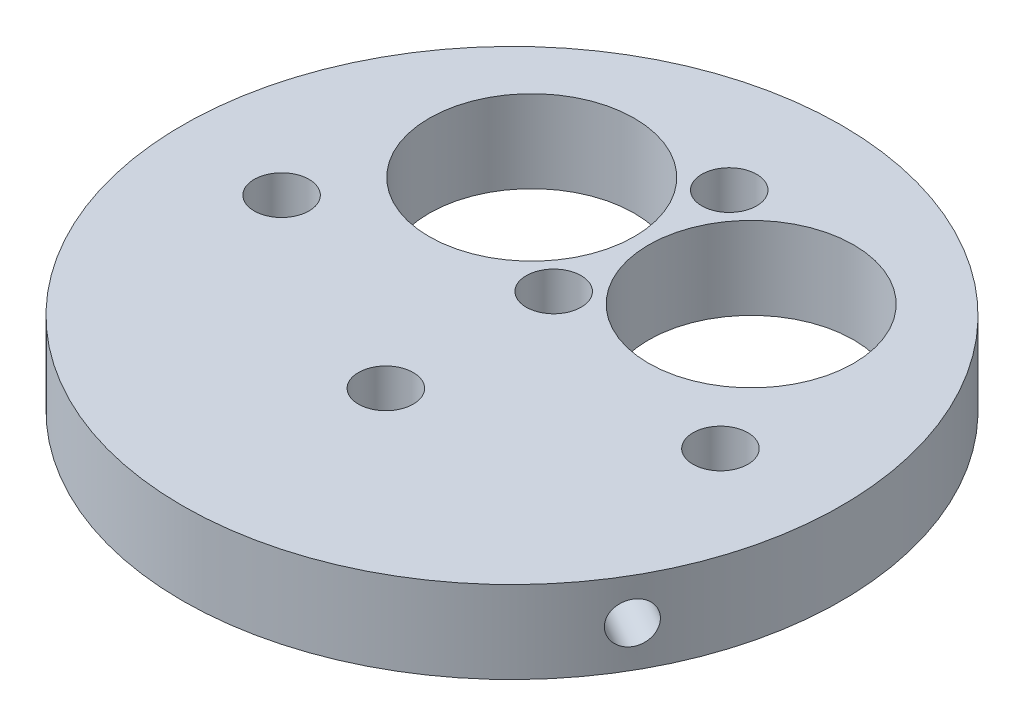
SolidWorks part; units mm, degrees
material "G10 Fiberglass"
ref_plane "Front Plane" through (0, 0, 0) normal (0, 0, 1) x (1, 0, 0)
ref_plane "Top Plane" through (0, 0, 0) normal (0, 1, 0) x (1, 0, 0)
ref_plane "Right Plane" through (0, 0, 0) normal (1, 0, 0) x (0, 0, -1)
ref_axis "Axis1" through (0, 55, 0) along (0, -1, 0)
sketch "Sketch1" plane through (0, 0, 0) normal (0, 0, 1) x (1, 0, 0)
  line L0 (0, 0) -> (38.1508, 0)
  line L3 (38.1508, 0) -> (38.1508, 9.525)
  line L4 (38.1508, 9.525) -> (0, 9.525)
  line L5 (0, 55) -> (0, -55) construction
  line L6 (0, 9.525) -> (0, 0)
  line L7 (0, 0) -> (0, 21.2966) construction
  dimension "D1" = 76.3016
  dimension "D2" = 9.525
revolve "Revolve1" add sketch "Sketch1" angle 360 about L7
sketch "Sketch2" plane through (0, 9.525, 0) normal (0, 1, 0) x (1, 0, 0)
  line L0 (-12.7, 14.986) -> (12.7, 14.986) construction
  line L1 (0, 25.146) -> (0, 4.826) construction
  line L2 (-12.7, 14.986) -> (12.7, 14.986) construction
  line L3 (-12.7, 28.956) -> (12.7, 28.956) construction
  line L4 (-12.7, 1.016) -> (12.7, 1.016) construction
  circle A0 centre (-12.7, 14.986) radius 11.8745
  circle A1 centre (0, 0) radius 38.1508
  circle A3 centre (12.7, 14.986) radius 11.8745
  circle A4 centre (0, 25.146) radius 3.175
  circle A5 centre (0, 4.826) radius 3.175
  arc A6 (-12.7, 28.956) -> (-12.7, 1.016) centre (-12.7, 14.986) ccw construction
  arc A7 (12.7, 1.016) -> (12.7, 28.956) centre (12.7, 14.986) ccw construction
  circle A8 centre (0, -14.605) radius 3.175
  circle A9 centre (0, 0) radius 34.163 construction
  circle A11 centre (0, 0) radius 38.1508 construction
  point P11 (0, 14.986)
  point P12 (0, 14.986)
  point P15 (0, 14.986)
  dimension "D2" = 23.749
  dimension "D3" = 23.749
  dimension "D5" = 6.35
  dimension "D6" = 6.35
  dimension "D11" = 6.35
  dimension "D4" = 25.4
  dimension "D7" = 20.32
  dimension "D8" = 25.4
  dimension "D9" = 27.94
  dimension "D10" = 14.605
  dimension "D12" = 1.016
  dimension "D1" = 0
extrude "Cut-Extrude1" cut sketch "Sketch2" against normal through all both and the other way through all
sketch "Sketch3" plane through (0, 9.525, 0) normal (0, 1, 0) x (1, 0, 0)
  circle A0 centre (-25.4, -1.27) radius 3.175
  circle A1 centre (25.4, -1.27) radius 3.175
  dimension "D1" = 6.35
  dimension "D2" = 6.35
  dimension "D3" = 50.8
  dimension "D4" = 1.27
extrude "Cut-Extrude2" cut sketch "Sketch3" against normal through all both
ref_plane "Mid Plane" through (0, 4.7625, 0) normal (0, 1, 0) x (-1, 0, 0)
ref_plane "Threaded Insert Plane" through (33.0396, 0, 19.0754) normal (0.866, 0, 0.5) x (0, -1, 0)
sketch "Sketch4" plane through (33.0396, 0, 19.0754) normal (0.866, 0, 0.5) x (0, -1, 0)
  line L0 (-55, 0) -> (55, 0) construction
  circle A0 centre (-4.7625, 0) radius 2.3749
  dimension "D2" = 4.7498
  dimension "D1" = 4.7625
extrude "Cut-Extrude3" cut sketch "Sketch4" against normal blind 6.35
pattern_circular "CirPattern1" count 3 over 360 about axis through (0, 55, 0) along (0, -1, 0) of "Cut-Extrude3"
ref_plane "Shear Pin Alignment Plane 1" through (-19.0754, 0, 33.0396) normal (-0.5, 0, 0.866) x (0.866, 0, 0.5)
ref_plane "Shear Pin Alignment Plane 2" through (0, 0, 0) normal (-0.5, 0, 0.866) x (0.866, 0, 0.5)
equation "\"D3@Sketch2\"=\"D2@Sketch2\""
equation "\"D6@Sketch2\"=\"D5@Sketch2\""
